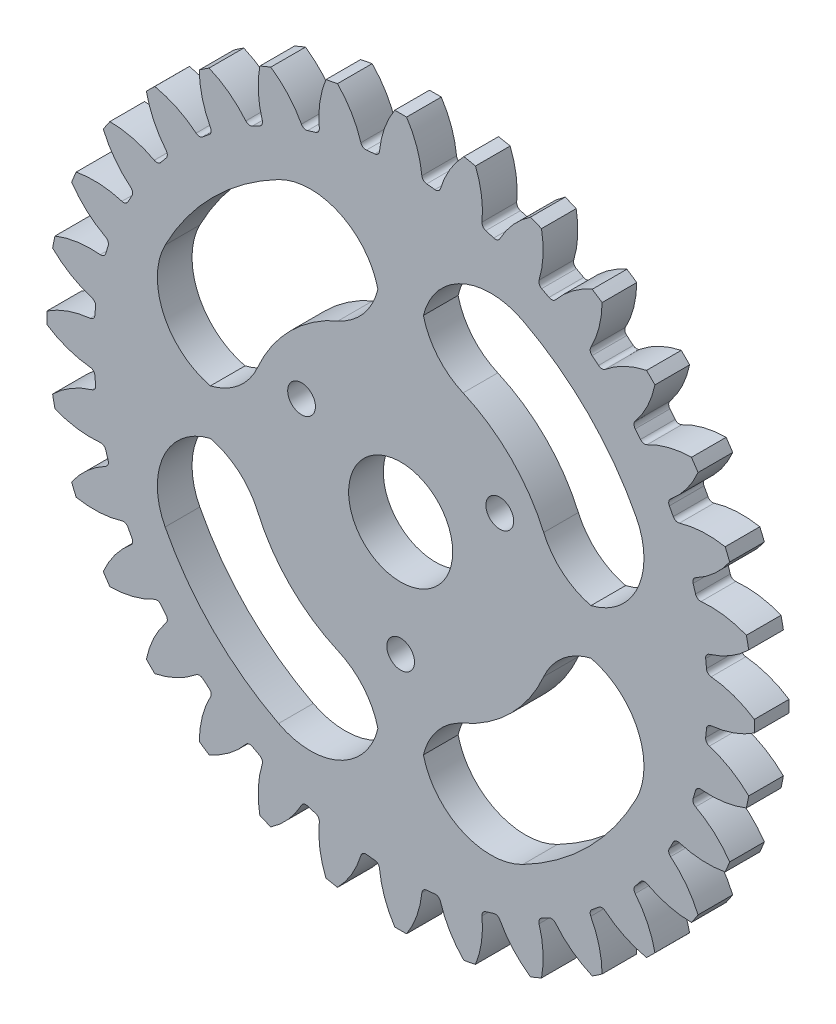
SolidWorks part; units mm, degrees
ref_plane "정면" through (0, 0, 0) normal (0, 0, 1) x (1, 0, 0)
ref_plane "윗면" through (0, 0, 0) normal (0, 1, 0) x (1, 0, 0)
ref_plane "우측면" through (0, 0, 0) normal (1, 0, 0) x (0, 0, -1)
sketch "스케치1" plane through (0, 0, 0) normal (0, 0, 1) x (1, 0, 0)
  line L0 (0, 56.6366) -> (0, -59.1981) construction
  line L1 (2.355, 47.9422) -> (2.355, -59.1981) construction
  line L2 (0.855, 50.9928) -> (0.855, -59.1981) construction
  line L3 (3.105, 44.1409) -> (3.105, -59.1981) construction
  line L4 (3.105, 56.6366) -> (3.105, -59.1981) construction
  line L5 (2.355, 56.6366) -> (2.355, -59.1981) construction
  line L6 (0.855, 56.6366) -> (0.855, -59.1981) construction
  circle A0 centre (0, 0) radius 48 construction
  circle A1 centre (0, 0) radius 51
  circle A2 centre (0, 0) radius 44.25
  arc A3 (0.855, 50.9928) -> (3.105, 44.1409) centre (-10.7861, 43.3748) cw
  arc A4 (-0.855, 50.9928) -> (-3.105, 44.1409) centre (10.7861, 43.3748) ccw
  dimension "D1" = 96
  dimension "D2" = 102
  dimension "D3" = 88.5
  dimension "D4" = 2.355
  dimension "D5" = 1.5
  dimension "D6" = 0.75
extrude "보스-돌출1" add sketch "스케치1" along normal blind 5 contours A2 region at (0, 0, 0)
extrude "보스-돌출2" add sketch "스케치1<3>" along normal blind 5 contours A1 A4 A2 A3 region at (0, 47.0624, 0)
sketch "스케치1<3>" plane through (0, 0, 0) normal (0, 0, 1) x (1, 0, 0) same geometry as "스케치1"
fillet "필렛1" radius 0.75 2 edges at (-3.105, 44.1409, 2.5) (3.105, 44.1409, 2.5)
sketch "스케치3" plane through (0, 0, 5) normal (0, 0, 1) x (1, 0, 0)
  line L0 (0, 38.25) -> (0, 22.5) construction
  line L1 (38.25, 0) -> (14, 0) construction
  line L2 (-3, 38.1322) -> (-3, 22.2991)
  line L3 (3, 38.1322) -> (3, 22.2991)
  line L4 (38.1322, 3) -> (22.2991, 3)
  line L5 (38.1322, -3) -> (22.2991, -3)
  line L6 (63.8113, 3) -> (-65.9933, 3) construction
  line L7 (63.8113, -3) -> (-65.9933, -3) construction
  line L8 (3, 58.3952) -> (3, -61.4529) construction
  line L9 (-3, 58.3952) -> (-3, -61.4529) construction
  line L10 (0, 58.3952) -> (0, -61.4529) construction
  line L11 (63.8113, 0) -> (-65.9933, 0) construction
  line L15 (-22.2991, 3) -> (-38.1322, 3)
  line L16 (-22.5, 0) -> (-38.25, 0) construction
  line L17 (-22.2991, -3) -> (-38.1322, -3)
  line L21 (3, -22.2991) -> (3, -38.1322)
  line L22 (0, -22.5) -> (0, -38.25) construction
  line L23 (-3, -22.2991) -> (-3, -38.1322)
  circle A0 centre (0, 0) radius 7.5
  circle A1 centre (0, 0) radius 22.5
  circle A3 centre (0, 0) radius 38.25
  circle A7 centre (0, 0) radius 16.5 construction
  circle A8 centre (0, -16.5) radius 2
  circle A10 centre (-14.2894, 8.25) radius 2
  circle A11 centre (14.2894, 8.25) radius 2
  point P53 (0, 0)
  dimension "D1" = 15
  dimension "D3" = 76.5
  dimension "D2" = 15
  dimension "D12" = 4
  dimension "D10" = 6
  dimension "D11" = 3
  dimension "D8" = 3
  dimension "D9" = 3
  dimension "D4" = 3
  dimension "D5" = 3
  dimension "D6" = 3
  dimension "D7" = 3
extrude "컷-돌출1" cut sketch "스케치3" against normal up to next contours A0 | L4 A3 L3 A1 | L2 A3 L15 A1 | L17 A3 L23 A1 | L21 A3 L5 A1 | A11 | A10 | A8 region at (-20.3268, 20.3268, 5) region at (20.3268, 20.3268, 5) region at (-20.3268, -20.3268, 5) region at (20.3268, -20.3268, 5) region at (0, 0, 5)
fillet "필렛2" radius 10 16 edges at (-3, 38.1322, 2.5) (-38.1322, 3, 2.5) (-38.1322, -3, 2.5) (-3, -38.1322, 2.5) (3, -38.1322, 2.5) (38.1322, -3, 2.5) (3, 38.1322, 2.5) (38.1322, 3, 2.5) (-22.2991, -3, 2.5) (-3, -22.2991, 2.5) (3, -22.2991, 2.5) (22.2991, -3, 2.5) (22.2991, 3, 2.5) (3, 22.2991, 2.5) (-22.2991, 3, 2.5) (-3, 22.2991, 2.5)
pattern_circular "원형 패턴1" count 32 over 360 about axis through (0, 0, -0.001) along (0, 0, 1) of "보스-돌출2", "필렛1"
